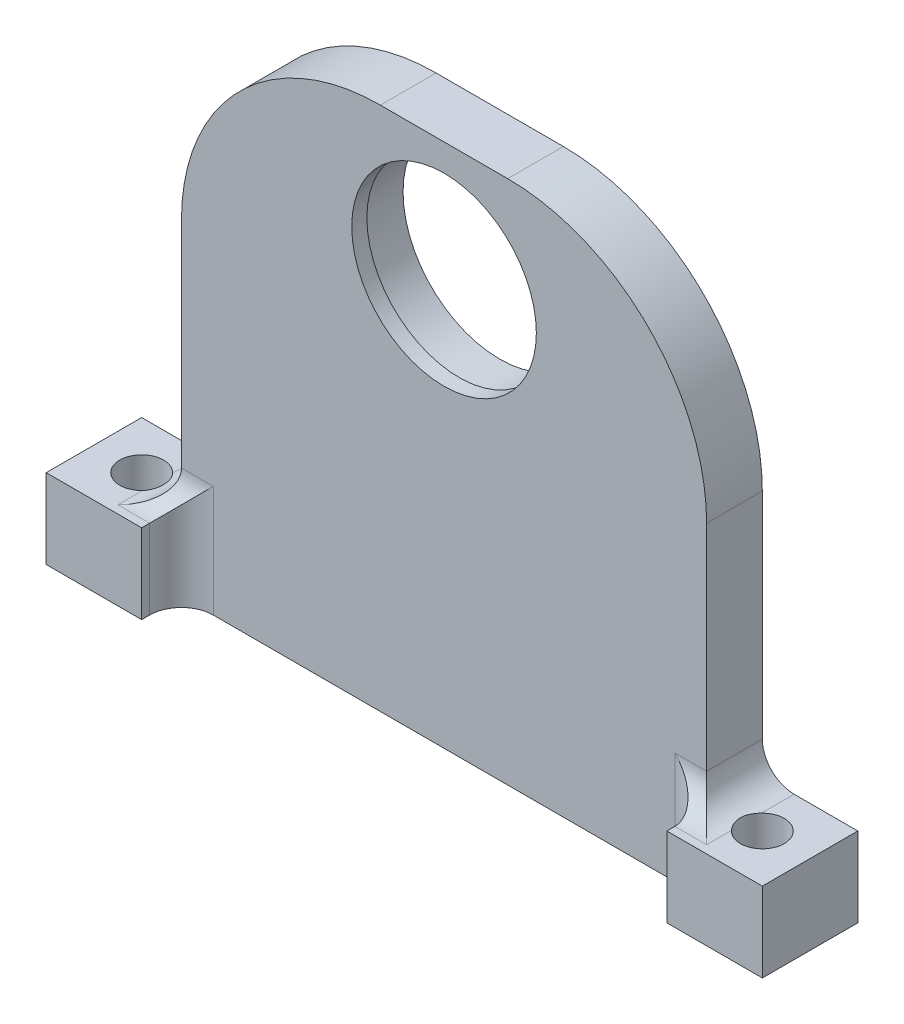
SolidWorks part; units mm, degrees
ref_plane "Front Plane" through (0, 0, 0) normal (0, 0, 1) x (1, 0, 0)
ref_plane "Top Plane" through (0, 0, 0) normal (0, 1, 0) x (1, 0, 0)
ref_plane "Right Plane" through (0, 0, 0) normal (1, 0, 0) x (0, 0, -1)
sketch "Sketch1" plane through (0, 0, 0) normal (0, 0, 1) x (1, 0, 0)
  line L1 (0, 15) -> (33, 15)
  line L2 (0, 15) -> (0, 11.6)
  line L3 (0, -51) -> (33, -51)
  line L4 (33, 15) -> (33, -51)
  line L7 (0, -11.6) -> (0, -51)
  arc A0 (0, -11.6) -> (0, 11.6) centre (0, 0) ccw
  dimension "D3" = 11.6
  dimension "D1" = 66
  dimension "D2" = 33
  dimension "D4" = 15
extrude "Boss-Extrude1" add sketch "Sketch1" along normal blind 7 separate body
sketch "Sketch2" plane through (0, 0, 0) normal (0, 0, -1) x (-1, 0, 0)
  line L0 (-33, -51) -> (-33, 15) construction
  line L1 (-45, 15) -> (-33, 15) construction
  line L2 (-45, 15) -> (-45, 5) construction
  line L3 (-45, 5) -> (-33, 5) construction
  line L4 (-33, 15) -> (-33, 5) construction
  line L5 (-33, -51) -> (-33, -41)
  line L6 (-33, -18) -> (-102.6679, -18) construction
  line L7 (-45, -41) -> (-33, -41)
  line L8 (-45, -51) -> (-45, -41)
  line L9 (-45, -51) -> (-33, -51)
  dimension "D1" = 10
  dimension "D2" = 12
extrude "Boss-Extrude2" add sketch "Sketch2" against normal blind 12
fillet "Fillet1" radius 4 1 edges at (33, -41, 3.5)
fillet "Fillet2" radius 4 2 edges at (33, -46, 7) (35, -41, 7)
sketch "Sketch3" plane through (0, -51, 0) normal (0, 1, 0) x (1, 0, 0)
  line L0 (33, -12) -> (33, 0) construction
  line L1 (33, 0) -> (0, 0) construction
  line L2 (33, -6) -> (45, -6) construction
  line L4 (39, -12) -> (39, 0) construction
  line L6 (33, -7) -> (33, 0) construction
  line L7 (37, 0) -> (45, 0) construction
  line L8 (33, -12) -> (45, -12) construction
  line L9 (45, -12) -> (45, 0) construction
  circle A0 centre (39, -6) radius 2.75
  point P2 (33, -6.0375)
  point P12 (39, 0)
  point P17 (39.376, 0)
  point P18 (39, -12)
  point P21 (45, -6)
  dimension "D1" = 5.5
extrude "Cut-Extrude1" cut sketch "Sketch3" along normal through all
sketch "Sketch4" plane through (0, 0, 0) normal (0, 0, -1) x (-1, 0, 0)
  circle A0 centre (0, 0) radius 12.15
  dimension "D1" = 24.3
extrude "Cut-Extrude2" cut sketch "Sketch4" against normal blind 5.1
fillet "Fillet3" radius 25 1 edges at (33, 15, 3.5)
mirror "Mirror1" about plane through (0, -11.6, 7) normal (1, 0, 0) of bodies 105
